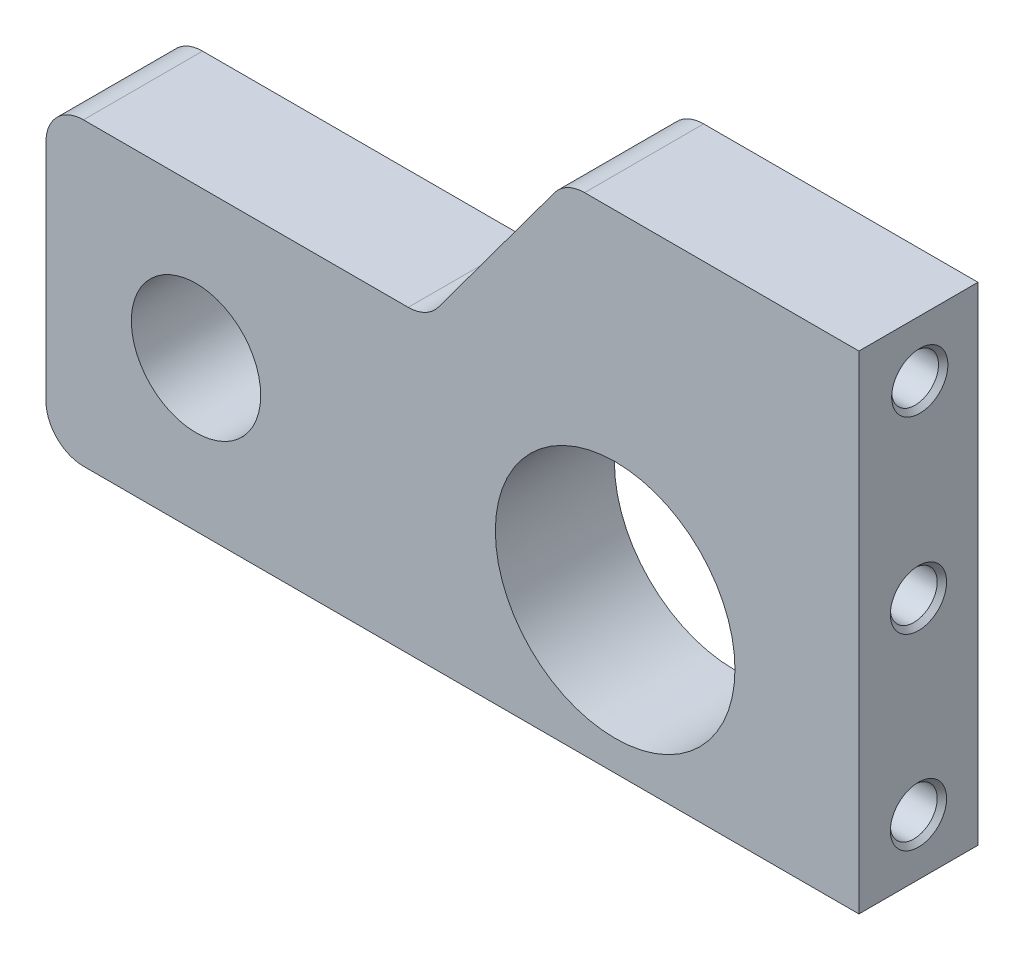
SolidWorks part; units mm, degrees
ref_plane "Front Plane" through (0, 0, 0) normal (0, 0, 1) x (1, 0, 0)
ref_plane "Top Plane" through (0, 0, 0) normal (0, 1, 0) x (1, 0, 0)
ref_plane "Right Plane" through (0, 0, 0) normal (1, 0, 0) x (0, 0, -1)
sketch "Sketch1" plane through (0, 0, 0) normal (0, 0, 1) x (1, 0, 0)
  line L0 (43.352, 8) -> (0, 8) construction
  line L1 (0, 0) -> (43.352, 0)
  line L2 (0, 0) -> (0, 16)
  line L3 (0, 16) -> (43.352, 16)
  line L4 (43.352, 0) -> (43.352, 16)
  circle A0 centre (8, 8) radius 3.45
  circle A1 centre (30.352, 8) radius 6.39
  dimension "D5" = 6.9
  dimension "D6" = 12.78
  dimension "D1" = 13
  dimension "D2" = 16
  dimension "D3" = 22.352
  dimension "D4" = 8
extrude "Boss-Extrude1" add sketch "Sketch1" along normal blind 6.35 contours L3 L4 L1 L2
extrude "Cut-Extrude1" cut sketch "Sketch1<6>" along normal blind 6.35 contours A0 L0 | L0 A0 | A1 region at (8, 6.5358, 0) region at (8, 9.4642, 0)
sketch "Sketch1<6>" plane through (0, 0, 0) normal (0, 0, 1) x (1, 0, 0) same geometry as "Sketch1"
fillet "Fillet1" radius 2 2 edges at (0, 16, 3.175) (0, 0, 3.175)
sketch "Sketch2" plane through (43.352, 0, 0) normal (1, 0, 0) x (0, 0, -1)
  line L0 (-6.35, 16) -> (0, 16) construction
  line L1 (-6.35, 0) -> (0, 0) construction
  line L4 (-6.35, 0) -> (-6.35, 16) construction
  circle A0 centre (-3.175, 13) radius 1.25
  circle A1 centre (-3.175, 3) radius 1.25
  dimension "D1" = 2.5
  dimension "D2" = 2.5
  dimension "D3" = 3
  dimension "D4" = 3
  dimension "D5" = 3.175
  dimension "D6" = 3.175
extrude "Cut-Extrude2" cut sketch "Sketch2" against normal blind 5
sketch "Sketch3" plane through (0, 0, 6.35) normal (0, 0, 1) x (1, 0, 0)
  line L0 (27.712, 26) -> (20.3263, 16)
  line L1 (43.352, 16) -> (27.712, 16)
  line L2 (43.352, 16) -> (43.352, 26)
  line L3 (43.352, 26) -> (27.712, 26)
  line L4 (27.712, 16) -> (27.712, 26)
  line L5 (2, 16) -> (43.352, 16) construction
  line M4 (43.352, 16) -> (2, 16)
  dimension "D1" = 10
extrude "Boss-Extrude2" add sketch "Sketch3" against normal blind 6.35 contours L4 L0 M4 | L4 L1 L2 L3 region at (25.2501, 19.3333, 6.35)
fillet "Fillet2" radius 2 2 edges at (20.3263, 16, 3.175) (27.712, 26, 3.175)
sketch "Sketch4" plane through (43.352, 0, 0) normal (1, 0, 0) x (0, 0, -1)
  line L0 (0, 26) -> (-6.35, 26) construction
  circle A0 centre (-3.1057, 23) radius 1.25
  dimension "D2" = 2.5
  dimension "D1" = 3
extrude "Cut-Extrude3" cut sketch "Sketch4" against normal blind 5
chamfer "Chamfer1" distance 0.25 angle 45 3 edges at (43.352, 3, 1.925) (43.352, 13, 1.925) (43.352, 23, 1.8557)
